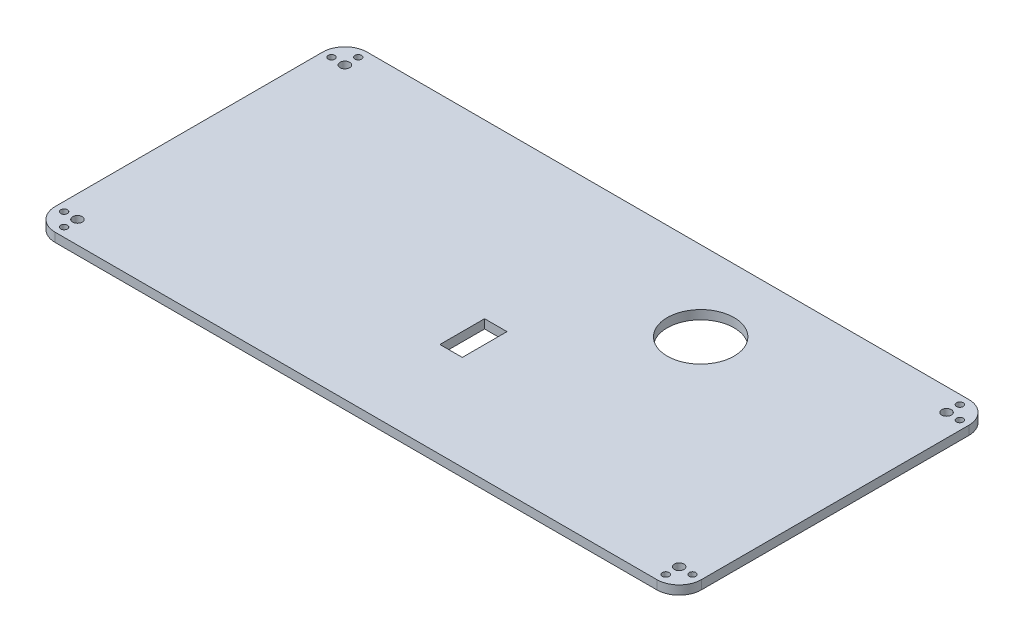
SolidWorks part; units mm, degrees
ref_plane "Front Plane" through (0, 0, 0) normal (0, 0, 1) x (1, 0, 0)
ref_plane "Top Plane" through (0, 0, 0) normal (0, 1, 0) x (1, 0, 0)
ref_plane "Right Plane" through (0, 0, 0) normal (1, 0, 0) x (0, 0, -1)
sketch "Sketch1" plane through (0, 0, 0) normal (0, 1, 0) x (1, 0, 0)
  line L0 (0, 0) -> (145, 0) construction
  line L1 (145, 0) -> (145, -60)
  line L2 (135, -70) -> (0, -70)
  line L3 (0, -70) -> (0, 0)
  line L4 (0, 0) -> (145, 0)
  line L5 (135, -60) -> (141, -60) construction
  line L6 (135, -60) -> (145, -70) construction
  arc A0 (135, -70) -> (145, -60) centre (135, -60) ccw
  arc A1 (135, -57.85) -> (137.15, -60) centre (135, -60) ccw
  circle A2 centre (135, -60) radius 2.15
  circle A3 centre (141, -60) radius 1.5
  circle A4 centre (135, -66) radius 1.5
  point P7 (145, -70)
  point P17 (145, -70)
  dimension "D4" = 10
  dimension "D5" = 4.3
  dimension "D7" = 3
  dimension "D1" = 145
  dimension "D2" = 70
  dimension "D3" = 145
  dimension "D6" = 6
extrude "Boss-Extrude1" add sketch "Sketch1" along normal blind 4 contours L2 A0 L1 L4 L3 A1 region at (72.1692, 0, 34.8552)
mirror "Mirror1" about plane through (0, 0, 0) normal (1, 0, 0) of "Boss-Extrude1"
mirror "Mirror2" about plane through (0, 0, 0) normal (0, 0, 1) of "Mirror1"
sketch "Sketch2" plane through (0, 4, 0) normal (0, 1, 0) x (1, 0, 0)
  line L0 (-4.55, -26.8091) -> (4.45, -26.8091) construction
  line L1 (4.45, -26.8091) -> (4.5, -7.7591) construction
  line L2 (4.5, -7.7591) -> (-4.5, -7.7591) construction
  line L3 (4.5, -14.8091) -> (4.5, -7.7591) construction
  line L4 (4.5, -7.7591) -> (-4.5, -7.7591) construction
  line L5 (-4.5, -7.7591) -> (-4.55, -26.8091) construction
  line L6 (-4.55, -26.8091) -> (-5.05, -26.8091) construction
  line L7 (-5.05, -26.8091) -> (-5.05, -27.3091) construction
  line L8 (4.5, -7.7591) -> (4.5, -7.2591) construction
  line L9 (4.5, -7.2591) -> (5, -7.2591) construction
  line L11 (-5.05, -27.3091) -> (5, -27.3091)
  line L12 (-5.05, -27.3091) -> (-5.05, -7.2591)
  line L13 (-5.05, -7.2591) -> (5, -7.2591)
  line L14 (5, -27.3091) -> (5, -7.2591)
  dimension "D1" = 0.5
  dimension "D2" = 0.5
  dimension "D3" = 0.5
  dimension "D4" = 0.5
extrude "Cut-Extrude5" cut sketch "Sketch2" against normal through all
sketch "Sketch3" plane through (0, 4, 0) normal (0, 1, 0) x (1, 0, 0)
  circle A0 centre (50.4863, 34.1799) radius 15
extrude "Cut-Extrude6" cut sketch "Sketch3" against normal blind 10 contours A0
